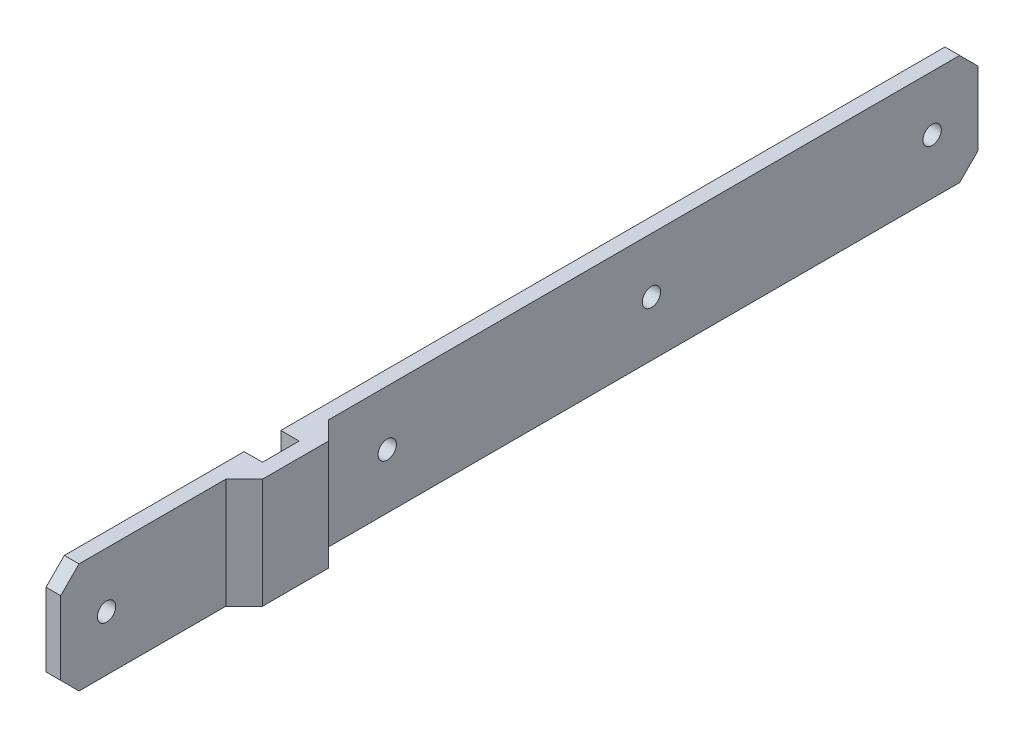
SolidWorks part; units mm, degrees
ref_plane "Alzado" through (0, 0, 0) normal (0, 0, 1) x (1, 0, 0)
ref_plane "Planta" through (0, 0, 0) normal (0, 1, 0) x (1, 0, 0)
ref_plane "Vista lateral" through (0, 0, 0) normal (1, 0, 0) x (0, 0, -1)
sketch "Croquis1" plane through (0, 0, 0) normal (0, 1, 0) x (1, 0, 0)
  line L0 (0, 0) -> (0, 186)
  line L1 (0, 186) -> (4, 186)
  line L2 (4, 186) -> (4, 4)
  line L3 (4, 4) -> (9, 4)
  line L4 (9, 4) -> (9, -14)
  line L5 (9, -14) -> (4, -14)
  line L6 (4, -14) -> (4, -64)
  line L7 (4, -64) -> (0, -64)
  line L8 (0, -64) -> (0, -10)
  line L9 (0, -10) -> (5, -10)
  line L10 (5, -10) -> (5, 0)
  line L11 (5, 0) -> (0, 0)
  point P8 (0, 0.3259)
  point P14 (0, -122.6983)
  dimension "D1" = 4
  dimension "D2" = 4
  dimension "D3" = 4
  dimension "D4" = 4
  dimension "D5" = 4
  dimension "D6" = 250
  dimension "D7" = 5
  dimension "D8" = 10
  dimension "D9" = 50
extrude "Saliente-Extruir1" add sketch "Croquis1" along normal mid plane 30
sketch "Croquis2" plane through (0, 0, 0) normal (1, 0, 0) x (0, 0, -1)
  line L0 (-51.5, 0) -> (25, 0) construction
  line L1 (25, 0) -> (97, 0) construction
  line L2 (97, 0) -> (173.5, 0) construction
  line L3 (-51.5, 0) -> (-64, 0) construction
  line L4 (-64, 15) -> (-64, -15) construction
  line L5 (173.5, 0) -> (186, 0) construction
  line L6 (186, 15) -> (186, -15) construction
  circle A0 centre (-51.5, 0) radius 2.5
  circle A1 centre (25, 0) radius 2.5
  circle A2 centre (97, 0) radius 2.5
  circle A3 centre (173.5, 0) radius 2.5
  dimension "D4" = 5
  dimension "D1" = 76.5
  dimension "D2" = 72
  dimension "D3" = 76.5
extrude "Cortar-Extruir2" cut sketch "Croquis2" along normal blind 30
chamfer "Chaflán1" distance 5 angle 45 6 edges at (2, -15, -186) (2, 15, -186) (2, -15, 64) (2, 15, 64) (4, 0, -4) (4, 0, 14)
